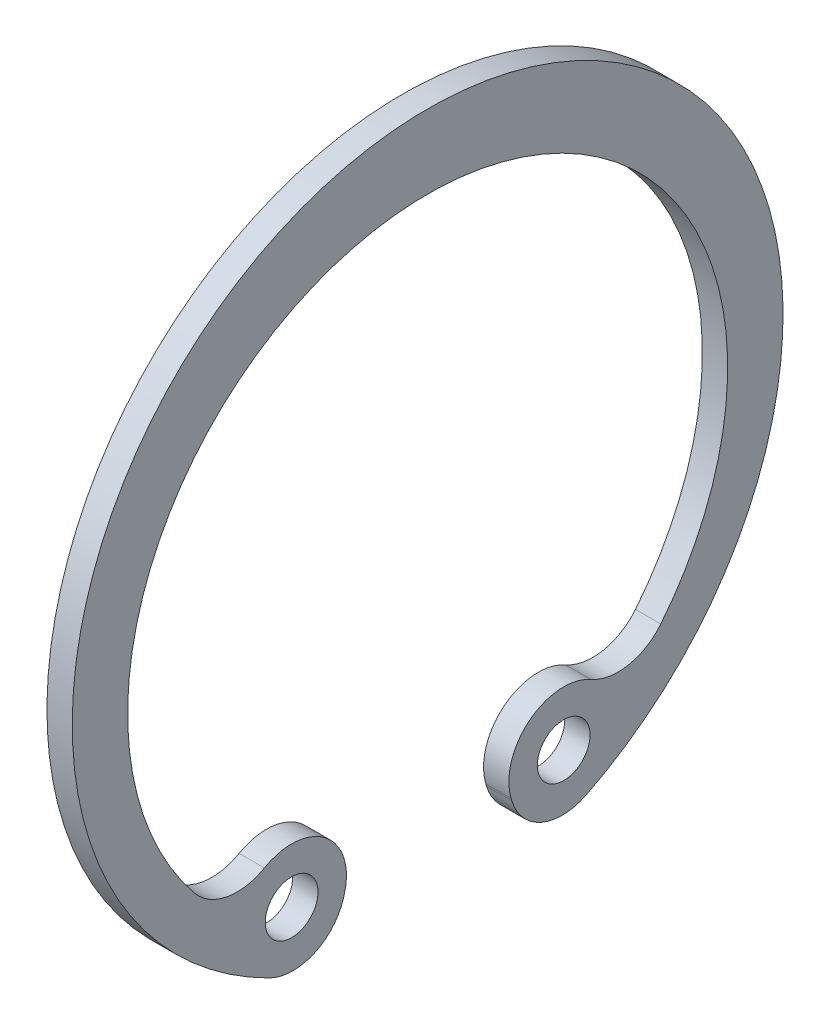
SolidWorks part; units mm, degrees
ref_plane "正面" through (0, 0, 0) normal (0, 0, 1) x (1, 0, 0)
ref_plane "平面" through (0, 0, 0) normal (0, 1, 0) x (1, 0, 0)
ref_plane "右側面" through (0, 0, 0) normal (1, 0, 0) x (0, 0, -1)
ref_plane "平面1" through (0, 0, 0) normal (1, 0, 0) x (0, 0, -1)
sketch "ｽｹｯﾁ1" plane through (0, 0, 0) normal (1, 0, 0) x (0, 0, -1)
  line L0 (-3.9896, -13.5557) -> (-3.9558, -13.4408)
  line L1 (3.9558, -13.4408) -> (3.9896, -13.5557)
  arc A0 (7.5008, -15.0884) -> (-7.5008, -15.0884) centre (0, 0) ccw
  arc A1 (-7.5008, -15.0884) -> (-3.9896, -13.5557) centre (-6.3879, -12.8498) ccw
  arc A2 (-3.9558, -13.4408) -> (-7.7412, -10.45) centre (-6.45, -12.7067) ccw
  arc A3 (-7.7412, -10.45) -> (-11.0525, -9.83) centre (-9.0324, -8.1932) cw
  arc A4 (-11.0525, -9.83) -> (11.0525, -9.83) centre (0, -0.875) cw
  arc A5 (11.0525, -9.83) -> (7.7412, -10.45) centre (9.0324, -8.1932) cw
  arc A6 (7.7412, -10.45) -> (3.9558, -13.4408) centre (6.45, -12.7067) ccw
  arc A7 (3.9896, -13.5557) -> (7.5008, -15.0884) centre (6.3879, -12.8498) ccw
  circle A8 centre (6.45, -12.7067) radius 1.25
  circle A9 centre (-6.45, -12.7067) radius 1.25
extrude "ﾎﾞｽ - 押し出し1" add sketch "ｽｹｯﾁ1" against normal blind 0.6 and the other way blind 0.6
